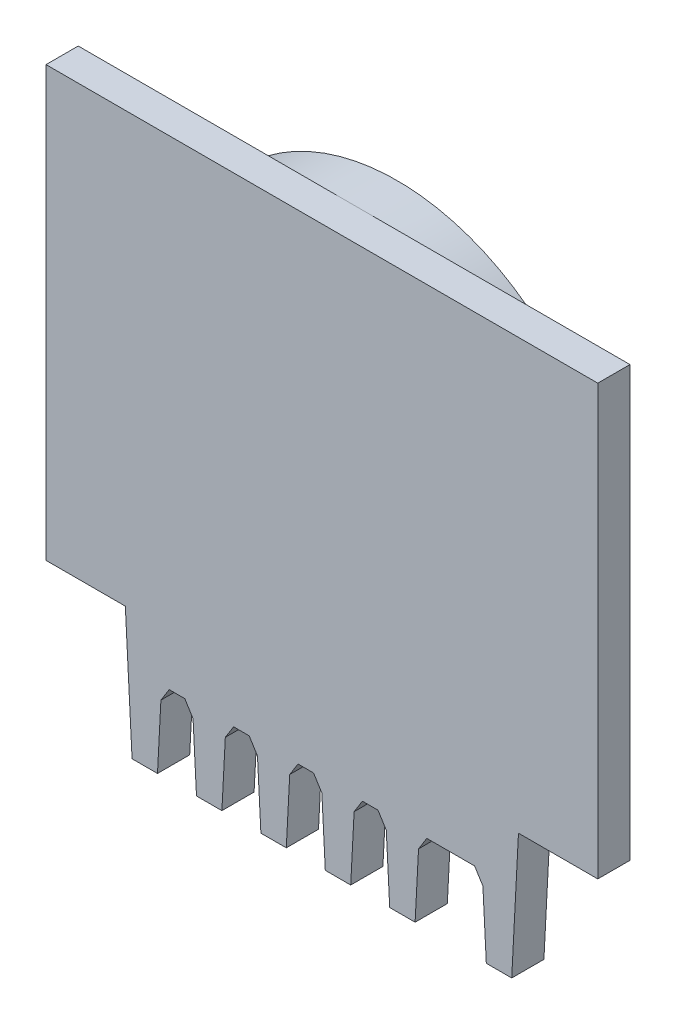
SolidWorks part; units mm, degrees
ref_plane "Front Plane" through (0, 0, 0) normal (0, 0, 1) x (1, 0, 0)
ref_plane "Top Plane" through (0, 0, 0) normal (0, 1, 0) x (1, 0, 0)
ref_plane "Right Plane" through (0, 0, 0) normal (1, 0, 0) x (0, 0, -1)
sketch "Sketch1" plane through (0, 0, 0) normal (0, 0, 1) x (1, 0, 0)
  line L0 (0, 0) -> (0, 26) construction
  line L1 (0, 26) -> (18.3124, 26) construction
  line L2 (18.3124, 26) -> (18.3124, 0) construction
  line L3 (18.3124, 0) -> (0, 0) construction
  line L4 (0, 3) -> (18.3124, 3) construction
  line L5 (0, 6) -> (18.3124, 6) construction
  line L6 (0.9062, 6) -> (0.9062, 0) construction
  line L7 (3.9062, 6) -> (3.9062, 0) construction
  line L8 (6.9062, 6) -> (6.9062, 0) construction
  line L9 (9.9062, 6) -> (9.9062, 0) construction
  line L10 (12.9062, 6) -> (12.9062, 0) construction
  line L11 (17.4062, 6) -> (17.4062, 0) construction
  line L12 (0.9062, 3) -> (3.9062, 3) construction
  line L13 (3.9062, 3) -> (6.9062, 3) construction
  line L14 (6.9062, 3) -> (9.9062, 3) construction
  line L15 (9.9062, 3) -> (12.9062, 3) construction
  line L16 (12.9062, 3) -> (17.4062, 3) construction
  line L17 (0.9062, 3) -> (0, 3) construction
  line L18 (17.4062, 3) -> (18.3124, 3) construction
  line L19 (2.4062, 3) -> (2.4062, 0) construction
  line L20 (5.4062, 3) -> (5.4062, 0) construction
  line L21 (8.4062, 3) -> (8.4062, 0) construction
  line L22 (11.4062, 3) -> (11.4062, 0) construction
  line L23 (15.1562, 3) -> (15.1562, 0) construction
  line L24 (14.4062, 3.75) -> (15.9062, 3.75) construction
  line L25 (0, 6) -> (0.3144, 0)
  line L26 (0.3144, 0) -> (1.4979, 0)
  line L27 (1.4979, 0) -> (1.6572, 3.0393)
  line L28 (3.1552, 3.0393) -> (3.3144, 0)
  line L29 (3.3144, 0) -> (4.4979, 0)
  line L30 (4.4979, 0) -> (4.6572, 3.0393)
  line L31 (6.1552, 3.0393) -> (6.3144, 0)
  line L32 (6.3144, 0) -> (7.4979, 0)
  line L33 (7.4979, 0) -> (7.6572, 3.0393)
  line L34 (9.1552, 3.0393) -> (9.3144, 0)
  line L35 (9.3144, 0) -> (10.4979, 0)
  line L36 (10.4979, 0) -> (10.6572, 3.0393)
  line L37 (12.1552, 3.0393) -> (12.3144, 0)
  line L38 (12.3144, 0) -> (13.4979, 0)
  line L39 (13.4979, 0) -> (13.6572, 3.0393)
  line L40 (16.6552, 3.0393) -> (16.8144, 0)
  line L41 (16.8144, 0) -> (17.9979, 0)
  line L42 (17.9979, 0) -> (18.3124, 6)
  line L44 (1.6572, 3.0393) -> (2.0426, 3.656)
  line L45 (0, 6) -> (-3.6938, 6)
  line L46 (-3.6938, 26) -> (22.0062, 26)
  line L47 (-3.6938, 6) -> (-3.6938, 26)
  line L48 (9.1562, 26) -> (9.1562, 6) construction
  line L49 (2.0426, 3.656) -> (2.7698, 3.656)
  line L50 (2.7698, 3.656) -> (3.1552, 3.0393)
  line L51 (4.6572, 3.0393) -> (5.0426, 3.656)
  line L52 (5.0426, 3.656) -> (5.7698, 3.656)
  line L53 (5.7698, 3.656) -> (6.1552, 3.0393)
  line L54 (7.6572, 3.0393) -> (8.0426, 3.656)
  line L55 (8.0426, 3.656) -> (8.7698, 3.656)
  line L56 (8.7698, 3.656) -> (9.1552, 3.0393)
  line L57 (10.6572, 3.0393) -> (11.0426, 3.656)
  line L58 (11.0426, 3.656) -> (11.7698, 3.656)
  line L59 (11.7698, 3.656) -> (12.1552, 3.0393)
  line L60 (13.6572, 3.0393) -> (14.0426, 3.656)
  line L61 (14.0426, 3.656) -> (16.2698, 3.656)
  line L62 (16.2698, 3.656) -> (16.6552, 3.0393)
  line L63 (18.3124, 6) -> (22.0062, 6)
  line L64 (22.0062, 6) -> (22.0062, 26)
  arc A0 (3.1552, 3.0393) -> (1.6572, 3.0393) centre (2.4062, 3) ccw construction
  arc A1 (6.1552, 3.0393) -> (4.6572, 3.0393) centre (5.4062, 3) ccw construction
  arc A2 (9.1552, 3.0393) -> (7.6572, 3.0393) centre (8.4062, 3) ccw construction
  arc A3 (12.1552, 3.0393) -> (10.6572, 3.0393) centre (11.4062, 3) ccw construction
  arc A4 (13.6572, 3.0393) -> (14.4062, 3.75) centre (14.4062, 3) cw construction
  arc A5 (16.6552, 3.0393) -> (15.9062, 3.75) centre (15.9062, 3) ccw construction
  circle A7 centre (9.1562, 16) radius 10 construction
  dimension "D7" = 0.75
  dimension "D11" = 20
  dimension "D1" = 3
  dimension "D2" = 6
  dimension "D4" = 3
  dimension "D5" = 25.7
  dimension "D6" = 4.5
  dimension "D8" = 3
  dimension "D9" = 18.3124
  dimension "D10" = 26
extrude "Boss-Extrude1" add sketch "Sketch1" along normal blind 1.5
sketch "Sketch3" plane through (0, 0, 0) normal (0, 0, 1) x (1, 0, 0)
  line L0 (-0.4005, 6) -> (18.7129, 6)
  line L1 (18.7129, 3) -> (-0.4005, 3) construction
  line L2 (-0.4005, 0) -> (18.7129, 0) construction
  line L3 (-0.4005, -0.5) -> (18.7129, -0.5) construction
  line L4 (18.7129, -0.5) -> (18.7129, 6) construction
  line L5 (-0.4005, 6) -> (-0.4005, -0.5) construction
  line L6 (18.3124, 0) -> (0, 0) construction
  line L7 (0, 3) -> (18.3124, 3) construction
  line L8 (0, 6) -> (18.3124, 6) construction
  line L9 (0.3407, -0.5) -> (0, 6) construction
  line L10 (18.3124, 6) -> (17.9717, -0.5) construction
  line L11 (17.9979, 0) -> (18.3124, 6) construction
  line L12 (0, 6) -> (0.3144, 0) construction
  line L13 (5.4062, 6) -> (5.4062, -0.5) construction
  line L14 (3.9062, 6) -> (3.9062, -0.5) construction
  line L15 (5.4062, 3) -> (5.4062, 0) construction
  line L16 (3.1572, 3) -> (3.3407, -0.5) construction
  line L17 (2.7567, 3) -> (2.9401, -0.5)
  line L18 (3.1552, 3.0393) -> (3.3144, 0) construction
  line L19 (2.9401, -0.5) -> (4.8723, -0.5)
  line L20 (4.8723, -0.5) -> (5.0557, 3)
  line L21 (2.8484, 1.25) -> (3.2478, 1.2709) construction
  line L22 (5.9401, -0.5) -> (5.7567, 3)
  line L26 (7.8723, -0.5) -> (5.9401, -0.5)
  line L27 (8.0557, 3) -> (7.8723, -0.5)
  line L30 (2.4062, -0.5) -> (2.4062, 6) construction
  line L31 (2.4062, 3) -> (2.4062, 0) construction
  line L32 (8.4062, 6) -> (8.4062, -0.5) construction
  line L34 (11.4062, -0.5) -> (11.4062, 6) construction
  line L35 (15.1562, -0.5) -> (15.1562, 6) construction
  line L36 (8.4062, 3) -> (8.4062, 0) construction
  line L37 (11.4062, 3) -> (11.4062, 0) construction
  line L38 (15.1562, 3) -> (15.1562, 0) construction
  line L39 (10.8723, -0.5) -> (11.0557, 3)
  line L40 (8.9401, -0.5) -> (10.8723, -0.5)
  line L41 (8.7567, 3) -> (8.9401, -0.5)
  line L42 (11.9401, -0.5) -> (11.7567, 3)
  line L43 (13.8723, -0.5) -> (11.9401, -0.5)
  line L44 (14.0557, 3) -> (13.8723, -0.5)
  line L45 (16.4401, -0.5) -> (18.3723, -0.5)
  line L46 (16.2567, 3) -> (16.4401, -0.5)
  line L47 (18.3723, -0.5) -> (18.7129, 6)
  line L48 (1.8723, -0.5) -> (-0.0599, -0.5)
  line L49 (2.0557, 3) -> (1.8723, -0.5)
  line L50 (-0.0599, -0.5) -> (-0.4005, 6)
  line L51 (16.2567, 3) -> (14.0557, 3)
  line L52 (11.7567, 3) -> (11.0557, 3)
  line L53 (8.7567, 3) -> (8.0557, 3)
  line L54 (5.7567, 3) -> (5.0557, 3)
  line L55 (2.7567, 3) -> (2.0557, 3)
  dimension "D1" = 0.5
  dimension "D2" = 0.4
ref_plane "Plane1" through (3.9062, 0, 0) normal (1, 0, 0) x (0, 0, -1)
sketch "Sketch4" plane through (3.9062, 0, 0) normal (1, 0, 0) x (0, 0, -1)
  line L0 (0, 6) -> (0, -0.5) construction
  line L1 (0.6, 6) -> (-2.1, 6) construction
  line L2 (0.6, 6) -> (0.6, -0.5) construction
  line L3 (0.6, -0.5) -> (-2.1, -0.5) construction
  line L4 (-2.1, 6) -> (-2.1, -0.5) construction
  line L5 (-0.75, -0.5) -> (-0.75, 6) construction
  line L6 (-1.5, 6) -> (-1.5, -0.5) construction
  line L7 (0.6, 2.4005) -> (-2.1, 2.4005) construction
  line L8 (0.3, 6) -> (0.3, -0.5) construction
  line L9 (0.6, 2.4005) -> (3.846, 6) construction
  line L10 (2.2302, 6) -> (0.6, 4.1923) construction
  line L11 (0.6, 4.1923) -> (1.7139, 3.1878) construction
  line L12 (1.7139, 3.1878) -> (4.25, 6)
  line L13 (4.25, 6) -> (0.6, 6) construction
  line L14 (0.3, 1) -> (-1.8, 1) construction
  line L15 (-2.1, 0) -> (0.6, 0) construction
  line L16 (1.7139, 3.1878) -> (1.4912, 3.3887)
  line L17 (1.4912, 3.3887) -> (0.6, 2.4005)
  line L18 (-3.2139, 3.1878) -> (-5.75, 6)
  line L19 (-3.2139, 3.1878) -> (-2.9912, 3.3887)
  line L20 (-2.9912, 3.3887) -> (-2.1, 2.4005)
  line L21 (-2.1, 6) -> (-5.75, 6) construction
  line L22 (0.6, 3.0724) -> (3.2401, 6) construction
  arc A0 (0.4965, 2.2224) -> (0.6, -0.5) centre (4.2, 1) ccw
  arc A1 (0.6, 2.4005) -> (0.4965, 2.2224) centre (0.9713, 2.0656) ccw
  arc A2 (-2.1, 2.4005) -> (-1.9965, 2.2224) centre (-2.4713, 2.0656) cw
  arc A3 (-1.9965, 2.2224) -> (-2.1, -0.5) centre (-5.7, 1) cw
  dimension "D6" = 0.5
  dimension "D1" = 0.6
  dimension "D2" = 0.3
  dimension "D3" = 1.5
  dimension "D4" = 1
  dimension "D5" = 0.3
  dimension "D7" = 10
sketch "Sketch5" plane through (0, 0, 0) normal (1, 0, 0) x (0, 0, -1)
  line L0 (2.2302, 6) -> (0.6, 4.1923) construction
  line L1 (0.6, 4.1923) -> (1.7139, 3.1878) construction
  line L2 (1.7139, 3.1878) -> (4.25, 6) construction
  line L3 (2.2302, 6) -> (0.6, 4.1923) construction
  line L4 (0.6, 4.1923) -> (1.7139, 3.1878) construction
  line L5 (1.7139, 3.1878) -> (4.25, 6) construction
ref_plane "Plane2" through (0, 2.6105, -2.3541) normal (0, 0.7426, -0.6697) x (1, 0, 0)
sketch "Sketch6" plane through (0, 2.6105, -2.3541) normal (0, 0.7426, -0.6697) x (1, 0, 0)
  line L1 (3.9062, -2.362) -> (3.9062, -0.862) construction
  line L2 (3.9062, -2.362) -> (3.9062, -5.0612) construction
  line L3 (4.6562, -5.0612) -> (3.1562, -5.0612)
  line L4 (4.6562, -1.612) -> (3.1562, -1.612) construction
  line L5 (3.1562, -1.612) -> (3.1562, -5.0612)
  line L6 (4.6562, -1.612) -> (4.6562, -5.0612)
  line L10 (2.4062, -5.0612) -> (15.1562, -5.0612) construction
  line L11 (15.1562, -5.0612) -> (15.1562, -0.862) construction
  line L12 (15.1562, -0.862) -> (2.4062, -0.862) construction
  line L13 (2.4062, -0.862) -> (2.4062, -5.0612) construction
  line L14 (15.1562, 0.3349) -> (15.1562, -4.0182) construction
  line L15 (2.4062, 0.3349) -> (2.4062, -4.0182) construction
  line L16 (11.4062, -5.0612) -> (11.4062, -0.862) construction
  line L17 (8.4062, -5.0612) -> (8.4062, -0.862) construction
  line L18 (5.4062, -5.0612) -> (5.4062, -0.862) construction
  line L19 (5.4062, -4.0182) -> (5.4062, 0.3349) construction
  line L20 (8.4062, -4.0182) -> (8.4062, 0.3349) construction
  line L21 (11.4062, 0.3349) -> (11.4062, -4.0182) construction
  line L22 (0.1562, -1.612) -> (0.1562, -5.0612)
  line L23 (0.1562, -5.0612) -> (1.6562, -5.0612)
  line L24 (1.6562, -1.612) -> (1.6562, -5.0612)
  line L25 (7.6562, -1.612) -> (7.6562, -5.0612)
  line L26 (6.1562, -5.0612) -> (7.6562, -5.0612)
  line L27 (6.1562, -1.612) -> (6.1562, -5.0612)
  line L28 (10.6562, -1.612) -> (10.6562, -5.0612)
  line L29 (10.6562, -5.0612) -> (9.1562, -5.0612)
  line L30 (9.1562, -1.612) -> (9.1562, -5.0612)
  line L31 (13.6562, -1.612) -> (13.6562, -5.0612)
  line L32 (12.1562, -5.0612) -> (13.6562, -5.0612)
  line L33 (12.1562, -1.612) -> (12.1562, -5.0612)
  line L34 (18.1562, -1.612) -> (18.1562, -5.0612)
  line L35 (18.1562, -5.0612) -> (16.6562, -5.0612)
  line L36 (16.6562, -1.612) -> (16.6562, -5.0612)
  circle A0 centre (3.9062, -1.612) radius 0.75 construction
  arc A1 (4.6562, -1.612) -> (3.1562, -1.612) centre (3.9062, -1.612) ccw
  arc A2 (0.1562, -1.612) -> (1.6562, -1.612) centre (0.9062, -1.612) cw
  arc A3 (6.1562, -1.612) -> (7.6562, -1.612) centre (6.9062, -1.612) cw
  arc A4 (10.6562, -1.612) -> (9.1562, -1.612) centre (9.9062, -1.612) ccw
  arc A5 (12.1562, -1.612) -> (13.6562, -1.612) centre (12.9062, -1.612) cw
  arc A6 (18.1562, -1.612) -> (16.6562, -1.612) centre (17.4062, -1.612) ccw
ref_plane "Plane3" through (0, 1.6223, -1.463) normal (0, 0.7426, -0.6697) x (1, 0, 0)
sketch "Sketch7" plane through (0, 1.6223, -1.463) normal (0, 0.7426, -0.6697) x (1, 0, 0)
  line L0 (3.1562, -1.612) -> (3.1562, -5.0612) construction
  line L1 (4.6562, -5.0612) -> (3.1562, -5.0612) construction
  line L2 (4.6562, -1.612) -> (4.6562, -5.0612) construction
  line L3 (3.1562, -1.612) -> (3.1562, -5.0612) construction
  line L4 (4.6562, -5.0612) -> (3.1562, -5.0612) construction
  line L5 (4.6562, -1.612) -> (4.6562, -5.0612) construction
  line L6 (3.9062, -0.862) -> (3.9062, -5.0612) construction
  line L7 (4.6562, -1.612) -> (3.1562, -1.612) construction
  line L8 (4.6562, -2.362) -> (3.1562, -2.362) construction
  line L9 (3.4562, -1.612) -> (3.4562, -2.362)
  line L10 (3.4562, -2.362) -> (4.3562, -2.362)
  line L11 (4.3562, -2.362) -> (4.3562, -1.612)
  line L12 (2.4062, -0.862) -> (2.4062, -5.0612) construction
  line L13 (2.4062, -5.0612) -> (15.1562, -5.0612) construction
  line L14 (15.1562, -0.862) -> (2.4062, -0.862) construction
  line L15 (5.4062, -5.0612) -> (5.4062, -0.862) construction
  line L16 (8.4062, -5.0612) -> (8.4062, -0.862) construction
  line L17 (11.4062, -5.0612) -> (11.4062, -0.862) construction
  line L18 (15.1562, -5.0612) -> (15.1562, -0.862) construction
  line L19 (2.4062, -0.862) -> (2.4062, -5.0612) construction
  line L20 (2.4062, -5.0612) -> (15.1562, -5.0612) construction
  line L21 (15.1562, -0.862) -> (2.4062, -0.862) construction
  line L22 (5.4062, -5.0612) -> (5.4062, -0.862) construction
  line L23 (8.4062, -5.0612) -> (8.4062, -0.862) construction
  line L24 (11.4062, -5.0612) -> (11.4062, -0.862) construction
  line L25 (15.1562, -5.0612) -> (15.1562, -0.862) construction
  line L26 (0.4562, -2.362) -> (0.4562, -1.612)
  line L27 (1.3562, -2.362) -> (0.4562, -2.362)
  line L28 (1.3562, -1.612) -> (1.3562, -2.362)
  line L29 (7.3562, -2.362) -> (6.4562, -2.362)
  line L30 (7.3562, -1.612) -> (7.3562, -2.362)
  line L31 (6.4562, -2.362) -> (6.4562, -1.612)
  line L32 (9.4562, -1.612) -> (9.4562, -2.362)
  line L33 (10.3562, -2.362) -> (10.3562, -1.612)
  line L34 (9.4562, -2.362) -> (10.3562, -2.362)
  line L35 (13.3562, -1.612) -> (13.3562, -2.362)
  line L36 (12.4562, -2.362) -> (12.4562, -1.612)
  line L37 (13.3562, -2.362) -> (12.4562, -2.362)
  line L38 (16.9562, -1.612) -> (16.9562, -2.362)
  line L39 (17.8562, -2.362) -> (17.8562, -1.612)
  line L40 (16.9562, -2.362) -> (17.8562, -2.362)
  arc A0 (4.6562, -1.612) -> (3.1562, -1.612) centre (3.9062, -1.612) ccw construction
  arc A1 (4.6562, -1.612) -> (3.1562, -1.612) centre (3.9062, -1.612) ccw construction
  circle A2 centre (3.9062, -1.612) radius 0.45 construction
  arc A3 (4.3562, -1.612) -> (3.4562, -1.612) centre (3.9062, -1.612) ccw
  arc A4 (0.4562, -1.612) -> (1.3562, -1.612) centre (0.9062, -1.612) cw
  arc A5 (6.4562, -1.612) -> (7.3562, -1.612) centre (6.9062, -1.612) cw
  arc A6 (10.3562, -1.612) -> (9.4562, -1.612) centre (9.9062, -1.612) ccw
  arc A7 (12.4562, -1.612) -> (13.3562, -1.612) centre (12.9062, -1.612) cw
  arc A8 (17.8562, -1.612) -> (16.9562, -1.612) centre (17.4062, -1.612) ccw
ref_plane "bisect" through (0, 0, 0.75) normal (0, 0, 1) x (1, 0, 0)
ref_plane "insert_surface" through (0, 6, 0) normal (0, 1, 0) x (1, 0, 0)
sketch "Sketch8" plane through (0, 6, 0) normal (0, 1, 0) x (1, 0, 0)
  line L0 (18.7129, -0.75) -> (-0.4005, -0.75) construction
  line L1 (-0.4005, 0.6) -> (18.7129, 0.6)
  line L2 (-0.4005, 0.6) -> (-0.4005, -2.1)
  line L3 (-0.4005, -2.1) -> (18.7129, -2.1)
  line L4 (18.7129, 0.6) -> (18.7129, -2.1)
  line L5 (9.1562, 0.6) -> (9.1562, -2.1) construction
  line L6 (0, 0) -> (18.3124, 0) construction
  line L7 (0, 0) -> (0, -1.5) construction
  line L8 (0, -1.5) -> (18.3124, -1.5) construction
  line L9 (18.3124, 0) -> (18.3124, -1.5) construction
  line L10 (18.7129, 0.3) -> (-0.4005, 0.3) construction
  line L11 (18.7129, -1.8) -> (-0.4005, -1.8) construction
sketch "Sketch9" plane through (0, 0, 0) normal (0, 0, 1) x (1, 0, 0)
  line L0 (18.3723, -0.5) -> (18.7129, 6) construction
  line L1 (-0.4005, 6) -> (18.7129, 6) construction
  line L2 (-0.0599, -0.5) -> (-0.4005, 6) construction
  line L3 (1.8723, -0.5) -> (-0.0599, -0.5) construction
  line L4 (2.0557, 3) -> (1.8723, -0.5) construction
  line L5 (2.7567, 3) -> (2.0557, 3) construction
  line L6 (2.7567, 3) -> (2.9401, -0.5) construction
  line L7 (2.9401, -0.5) -> (4.8723, -0.5) construction
  line L8 (4.8723, -0.5) -> (5.0557, 3) construction
  line L9 (5.7567, 3) -> (5.0557, 3) construction
  line L10 (5.9401, -0.5) -> (5.7567, 3) construction
  line L11 (7.8723, -0.5) -> (5.9401, -0.5) construction
  line L12 (8.0557, 3) -> (7.8723, -0.5) construction
  line L13 (8.7567, 3) -> (8.0557, 3) construction
  line L14 (8.7567, 3) -> (8.9401, -0.5) construction
  line L15 (8.9401, -0.5) -> (10.8723, -0.5) construction
  line L16 (10.8723, -0.5) -> (11.0557, 3) construction
  line L17 (11.7567, 3) -> (11.0557, 3) construction
  line L18 (11.9401, -0.5) -> (11.7567, 3) construction
  line L19 (13.8723, -0.5) -> (11.9401, -0.5) construction
  line L20 (14.0557, 3) -> (13.8723, -0.5) construction
  line L21 (16.2567, 3) -> (14.0557, 3) construction
  line L22 (16.2567, 3) -> (16.4401, -0.5) construction
  line L23 (16.4401, -0.5) -> (18.3723, -0.5) construction
  line L24 (18.3723, -0.5) -> (18.7129, 6)
  line L25 (-0.4005, 6) -> (18.7129, 6) construction
  line L26 (-0.0599, -0.5) -> (-0.4005, 6)
  line L27 (1.8723, -0.5) -> (-0.0599, -0.5)
  line L28 (2.0557, 3) -> (1.8723, -0.5)
  line L29 (2.7567, 3) -> (2.0557, 3) construction
  line L30 (2.7567, 3) -> (2.9401, -0.5)
  line L31 (2.9401, -0.5) -> (4.8723, -0.5)
  line L32 (4.8723, -0.5) -> (5.0557, 3)
  line L33 (5.7567, 3) -> (5.0557, 3) construction
  line L34 (5.9401, -0.5) -> (5.7567, 3)
  line L35 (7.8723, -0.5) -> (5.9401, -0.5)
  line L36 (8.0557, 3) -> (7.8723, -0.5)
  line L37 (8.7567, 3) -> (8.0557, 3) construction
  line L38 (8.7567, 3) -> (8.9401, -0.5)
  line L39 (8.9401, -0.5) -> (10.8723, -0.5)
  line L40 (10.8723, -0.5) -> (11.0557, 3)
  line L41 (11.7567, 3) -> (11.0557, 3) construction
  line L42 (11.9401, -0.5) -> (11.7567, 3)
  line L43 (13.8723, -0.5) -> (11.9401, -0.5)
  line L44 (14.0557, 3) -> (13.8723, -0.5)
  line L45 (16.2567, 3) -> (14.0557, 3) construction
  line L46 (16.2567, 3) -> (16.4401, -0.5)
  line L47 (16.4401, -0.5) -> (18.3723, -0.5)
  line L48 (16.2567, 3) -> (16.2567, 6)
  line L49 (14.0557, 3) -> (14.0557, 6)
  line L50 (11.7567, 3) -> (11.7567, 6)
  line L51 (18.7129, 6) -> (-0.4005, 6) construction
  line L52 (11.0557, 3) -> (11.0557, 6)
  line L53 (-0.4005, 6) -> (18.7129, 6) construction
  line L54 (8.7567, 3) -> (8.7567, 6)
  line L55 (8.0557, 3) -> (8.0557, 6)
  line L58 (5.7567, 3) -> (5.7567, 6)
  line L60 (5.0557, 3) -> (5.0557, 6)
  line L62 (15.1562, -0.5) -> (15.1562, 6) construction
  line L63 (15.1562, -0.5) -> (15.1562, 6) construction
  line L64 (2.7567, 3) -> (2.7567, 6)
  line L65 (2.0557, 3) -> (2.0557, 6)
  line L67 (18.7129, 6) -> (16.2567, 6)
  line L68 (14.0557, 6) -> (11.7567, 6)
  line L69 (11.0557, 6) -> (8.7567, 6)
  line L70 (8.0557, 6) -> (5.7567, 6)
  line L71 (5.0557, 6) -> (2.7567, 6)
  line L72 (2.0557, 6) -> (-0.4005, 6)
sketch "Sketch10" plane through (0, 0, 0) normal (0, 0, 1) x (1, 0, 0)
  circle A0 centre (9.1562, 16) radius 10
extrude "Boss-Extrude2" add sketch "Sketch10" against normal blind 2
